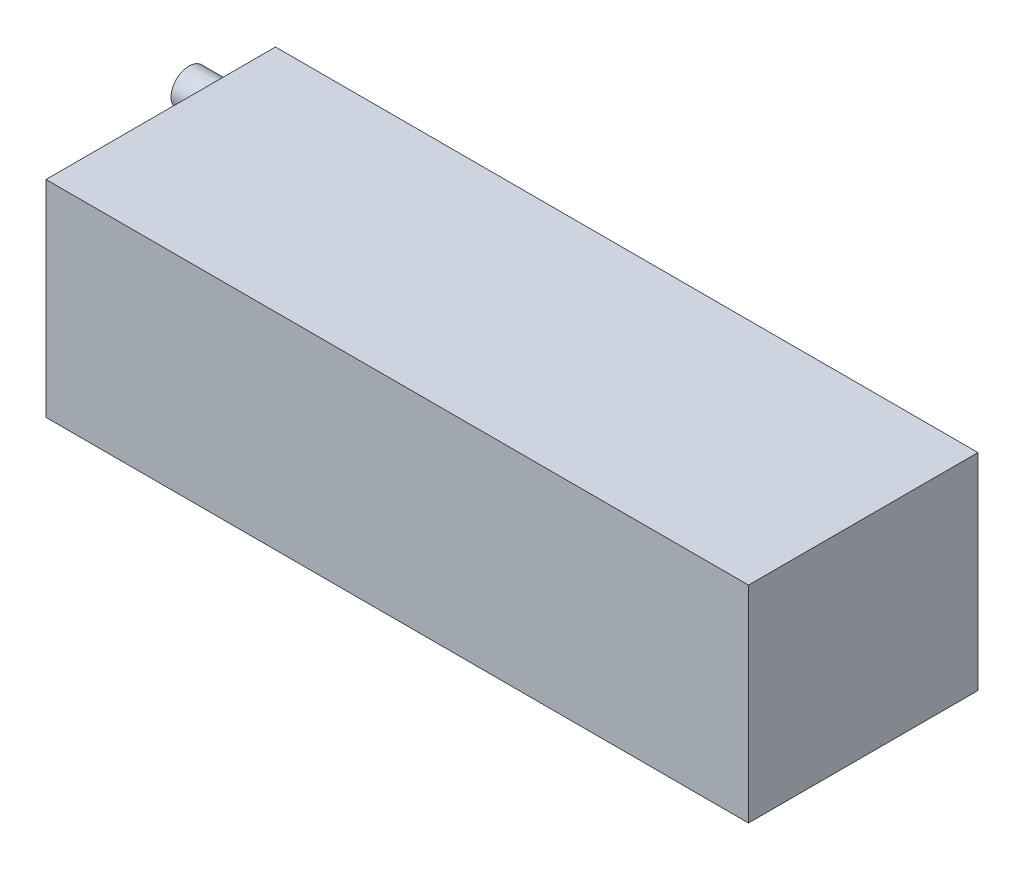
SolidWorks part; units mm, degrees
ref_plane "Front Plane" through (0, 0, 0) normal (0, 0, 1) x (1, 0, 0)
ref_plane "Top Plane" through (0, 0, 0) normal (0, 1, 0) x (1, 0, 0)
ref_plane "Right Plane" through (0, 0, 0) normal (1, 0, 0) x (0, 0, -1)
sketch "Sketch1" plane through (0, 0, 0) normal (0, 1, 0) x (1, 0, 0)
  line L1 (0, 0) -> (150, 0)
  line L2 (0, 0) -> (0, 49)
  line L3 (0, 49) -> (150, 49)
  line L4 (150, 0) -> (150, 49)
  dimension "D1" = 150
  dimension "D2" = 49
extrude "Boss-Extrude1" add sketch "Sketch1" along normal blind 44
sketch "Sketch2" plane through (0, 0, 0) normal (-1, 0, 0) x (0, 0, 1)
  circle A0 centre (-40.5294, 35.8869) radius 3.8245
  circle A1 centre (-40.5294, 8.9066) radius 3.8245
extrude "Boss-Extrude2" add sketch "Sketch2" along normal blind 10 separate body
ref_plane "Plane1" through (0, 0, -24.5) normal (0, 0, -1) x (-1, 0, 0)
ref_plane "Plane2" through (0, 22, 0) normal (0, 1, 0) x (1, 0, 0)
ref_plane "Plane3" through (75, 0, 0) normal (-1, 0, 0) x (0, 0, 1)
